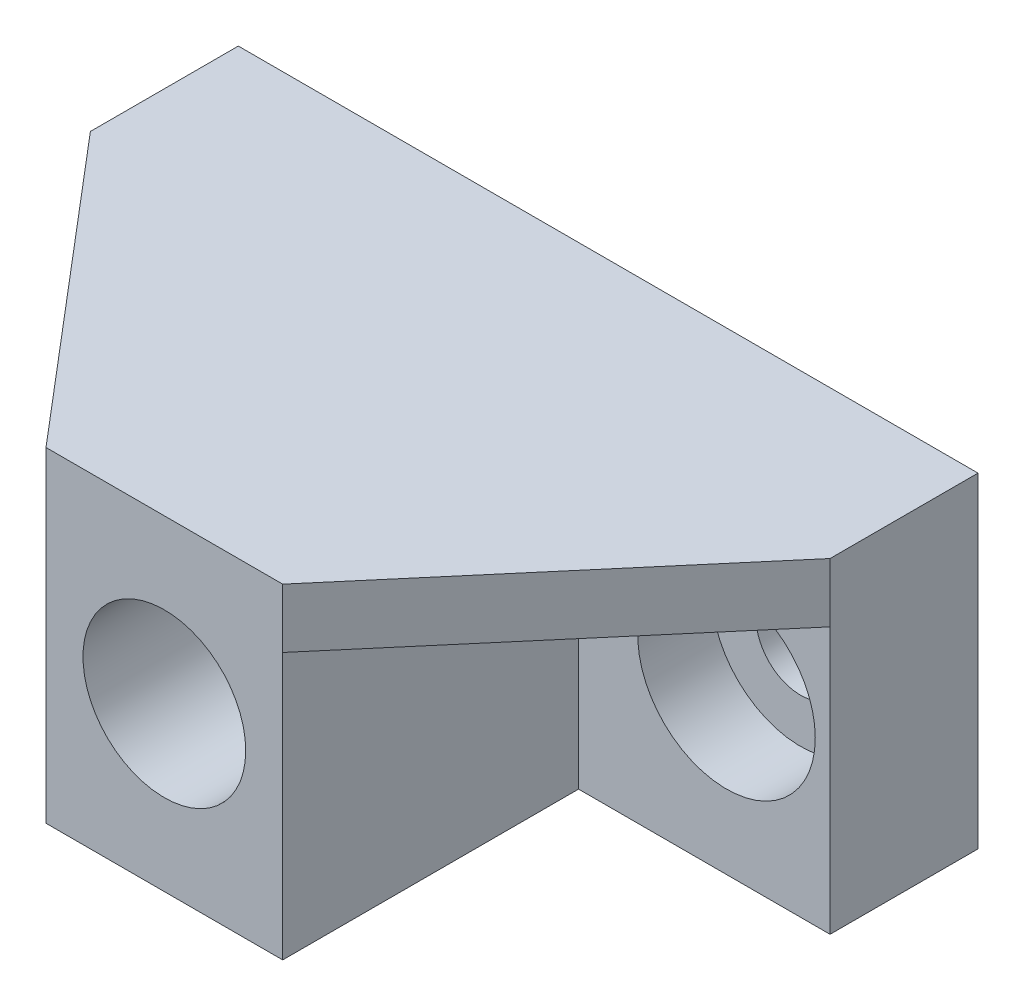
SolidWorks part; units mm, degrees
ref_plane "Спереди" through (0, 0, 0) normal (0, 0, 1) x (1, 0, 0)
ref_plane "Сверху" through (0, 0, 0) normal (0, 1, 0) x (1, 0, 0)
ref_plane "Справа" through (0, 0, 0) normal (1, 0, 0) x (0, 0, -1)
sketch "Эскиз1" plane through (0, 0, 0) normal (0, 0, 1) x (1, 0, 0)
  line L1 (-12.5, -12.5) -> (12.5, -12.5)
  line L2 (-12.5, -12.5) -> (-12.5, 12.5)
  line L3 (-12.5, 12.5) -> (12.5, 12.5)
  line L4 (12.5, -12.5) -> (12.5, 12.5)
  line L5 (-12.5, -12.5) -> (12.5, 12.5) construction
  line L6 (-12.5, 12.5) -> (12.5, -12.5) construction
  line L7 (-12.5, 12.5) -> (-4.5, 12.5)
  line L8 (-12.5, 12.5) -> (-12.5, -9.5)
  line L9 (-12.5, -9.5) -> (-4.5, -9.5)
  line L10 (-4.5, 12.5) -> (-4.5, -9.5)
  point P0 (0, 0)
  dimension "D1" = 25
  dimension "D2" = 25
  dimension "D3" = 8
  dimension "D4" = 22
extrude "Бобышка-Вытянуть1" add sketch "Эскиз1" along normal blind 10 contours L3 L10 L9 L2 L1 L4 | L10 L3 L2 L9 region at (3.3318, -0.588, 0) region at (-8.5, 1.5, 0)
extrude "Бобышка-Вытянуть2" add sketch "Эскиз1<3>" along normal blind 30 contours L10 L3 L2 L9 region at (-8.5, 1.5, 0)
sketch "Эскиз1<3>" plane through (0, 0, 0) normal (0, 0, 1) x (1, 0, 0) same geometry as "Эскиз1"
sketch "Эскиз2" plane through (0, 12.5, 0) normal (0, 1, 0) x (1, 0, 0)
  line L0 (12.5, -10) -> (-4.5, -30)
  line L1 (-4.5, -30) -> (-4.5, -10)
  line L2 (-4.5, -10) -> (12.5, -10)
extrude "Бобышка-Вытянуть3" add sketch "Эскиз2" against normal blind 4
sketch "Эскиз3" plane through (0, 0, 10) normal (0, 0, 1) x (1, 0, 0)
  line L0 (12.5, -12.5) -> (12.5, 8.5) construction
  line L1 (-4.5, 12.5) -> (12.5, 12.5) construction
  circle A0 centre (5.5, 1.5) radius 6
  dimension "D3" = 12
  dimension "D1" = 7
  dimension "D2" = 11
extrude "Вырез-Вытянуть1" cut sketch "Эскиз3" against normal blind 5
sketch "Эскиз4" plane through (0, 0, 5) normal (0, 0, 1) x (1, 0, 0)
  circle A2 centre (5.5, 1.5) radius 3
  circle A3 centre (5.5, 1.5) radius 3
  dimension "D1" = 3
extrude "Вырез-Вытянуть2" cut sketch "Эскиз4" against normal through all
mirror "Зеркальное отражение1" about plane through (-12.5, 0, 10) normal (-1, 0, 0) of "Вырез-Вытянуть2", "Бобышка-Вытянуть2", "Вырез-Вытянуть1", "Бобышка-Вытянуть1", "Бобышка-Вытянуть3"
sketch "Эскиз5" plane through (0, 0, 30) normal (0, 0, 1) x (1, 0, 0)
  line L0 (-12.5, 12.5) -> (-12.5, -9.5) construction
  line L1 (-20.5, 12.5) -> (-4.5, 12.5) construction
  line L2 (-4.5, -9.5) -> (-20.5, -9.5) construction
  circle A0 centre (-12.5, 1.5) radius 5.5
  dimension "D1" = 11
extrude "Вырез-Вытянуть3" cut sketch "Эскиз5" against normal through all
sketch "Эскиз6" plane through (0, -12.5, 0) normal (0, -1, 0) x (1, 0, 0)
  line L4 (-37.5, 0) -> (12.5, 0)
  line L5 (12.5, 0) -> (12.5, 10)
  line L6 (12.5, 10) -> (-37.5, 10)
  line L7 (-37.5, 10) -> (-37.5, 0)
  line L8 (-37.5, 0) -> (12.5, 0)
  line L9 (12.5, 0) -> (12.5, 10)
  line L10 (12.5, 10) -> (-37.5, 10)
  line L11 (-37.5, 10) -> (-37.5, 0)
  dimension "D1" = 0
extrude "Вырез-Вытянуть4" cut sketch "Эскиз6" against normal up to surface (3 mm away) up to face at (-10.5, -9.5, 20)
